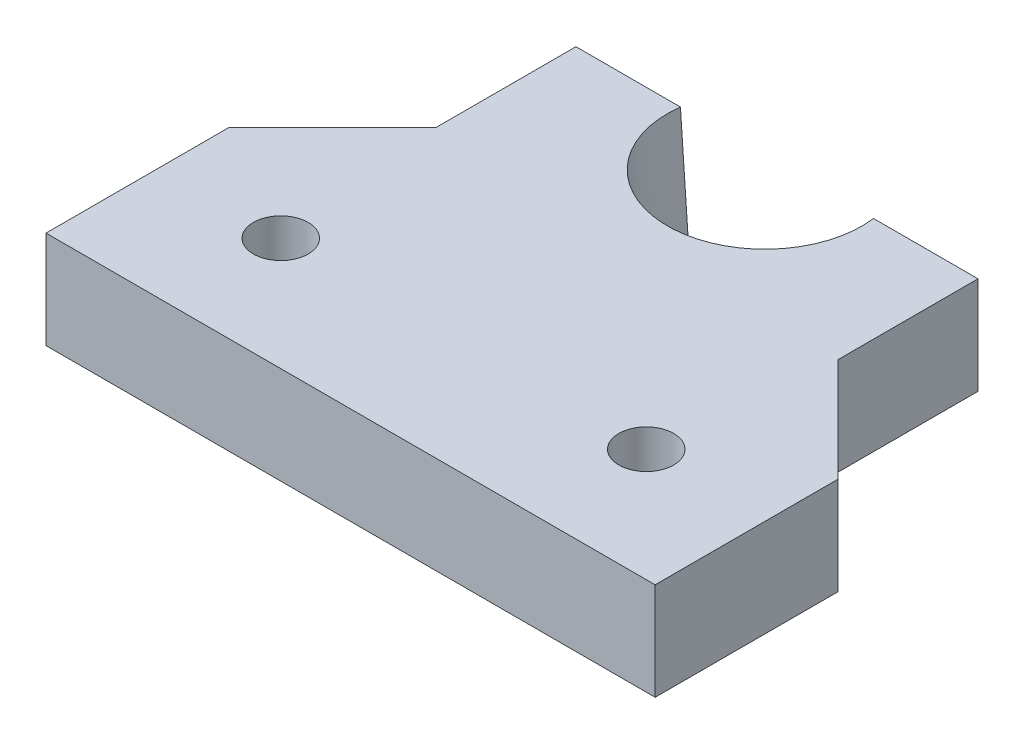
SolidWorks part; units mm, degrees
ref_plane "Front Plane" through (0, 0, 0) normal (0, 0, 1) x (1, 0, 0)
ref_plane "Top Plane" through (0, 0, 0) normal (0, 1, 0) x (1, 0, 0)
ref_plane "Right Plane" through (0, 0, 0) normal (1, 0, 0) x (0, 0, -1)
sketch "Sketch1" plane through (0, 0, 0) normal (0, 1, 0) x (1, 0, 0)
  line L2 (-25, 3.9263) -> (-25, -11.0737)
  line L3 (-25, -11.0737) -> (25, -11.0737)
  line L4 (25, 3.9263) -> (25, -11.0737)
  line L5 (-11.3635, 5.0335) -> (25, -11.0737) construction
  line L6 (-25, -11.0737) -> (25, 11.0737) construction
  line L7 (-16.5, 23.9263) -> (16.5, 23.9263)
  line L8 (-16.5, 23.9263) -> (-16.5, 12.4263)
  line L10 (16.5, 23.9263) -> (16.5, 12.4263)
  line L11 (-16.5, 23.9263) -> (10.3428, 12.1826) construction
  line L12 (-7.7224, 13.329) -> (16.5, 23.9263) construction
  line L13 (-16.5, 12.4263) -> (-25, 3.9263)
  line L14 (0, 0) -> (0, 34.1814) construction
  line L15 (16.5, 12.4263) -> (25, 3.9263)
  line L16 (0, 0) -> (0, -43.0894) construction
  line L17 (0, -11.0737) -> (0, -4.632) construction
  point P0 (0, 0)
  point P6 (0, 16.7075)
  dimension "D1" = 35
  dimension "D2" = 50
  dimension "D3" = 15
  dimension "D4" = 45
  dimension "D5" = 33
extrude "Boss-Extrude1" add sketch "Sketch1" along normal blind 8 contours L8 L13 L2 L3 L4 L15 L10 L7
sketch "Sketch2" plane through (0, 0, 0) normal (0, -1, 0) x (1, 0, 0)
  line L0 (-16.5, -23.9263) -> (16.5, -23.9263) construction
  line L1 (-10, -3.9263) -> (10, -3.9263)
  line L2 (-10, -3.9263) -> (-10, -23.9263)
  line L3 (-10, -23.9263) -> (10, -23.9263)
  line L4 (10, -3.9263) -> (10, -23.9263)
  line L5 (-10, -3.9263) -> (10, -23.9263) construction
  line L6 (-10, -23.9263) -> (10, -3.9263) construction
  line L7 (0, 0) -> (0, -53.5828) construction
  point P0 (0, -13.9263)
  dimension "D1" = 20
  dimension "D2" = 20
extrude "Boss-Extrude2" add sketch "Sketch2" along normal blind 2
fillet "Fillet1" radius 10 2 edges at (-10, -1, -3.9263) (10, -1, -3.9263)
sketch "Sketch3" plane through (0, -2, 0) normal (0, -1, 0) x (1, 0, 0)
  line L0 (0, 0) -> (0, -26.6551) construction
  line L1 (-20.6759, -21.4263) -> (25.4817, -21.4263) construction
  line L2 (-10, -23.9263) -> (10, -23.9263) construction
  circle A0 centre (0, -22.9263) radius 7.29
  dimension "D2" = 14.58
  dimension "D1" = 2.5
extrude "Cut-Extrude1" cut sketch "Sketch3" against normal through all draft 4 draft outward yes
sketch "Sketch4" plane through (0, 0, 0) normal (0, -1, 0) x (1, 0, 0)
  line L0 (0, 12.0517) -> (0, -23.3395) construction
  line L1 (15, 4.0737) -> (29.3934, 4.0737) construction
  line L2 (-25, 11.0737) -> (25, 11.0737) construction
  circle A0 centre (15, 1.804) radius 2.2697
  circle A1 centre (-15, 1.804) radius 2.2697
  dimension "D1" = 30
  dimension "D2" = 7
hole_wizard "CBORE for M5 Hex Head Bolt1" positions "3DSketch1" profile "Sketch5" counterbore size "M5" standard "ISO" end condition through all
sketch3d "3DSketch1"
  point P0 (-15, 0, 1.804)
  point P3 (15, 0, 1.804)
sketch "Sketch5" plane through (-15, 0, 1.804) normal (1, 0, 0) x (0, 0, -1)
  line L0 (0, 0) -> (0, 8)
  line L1 (0, 8) -> (2.25, 8)
  line L3 (2.25, 8) -> (2.25, 3)
  line L4 (2.25, 3) -> (5, 3)
  line L5 (5, 3) -> (5, 0)
  line L7 (5, 0) -> (0, 0)
  line L11 (0, -6.35) -> (0, 107.95) construction
  dimension "Thru Hole Dia." = 4.5
  dimension "Thru Hole Depth" = 8
  dimension "C'Bore Dia." = 10
  dimension "C'Bore Depth" = 3
